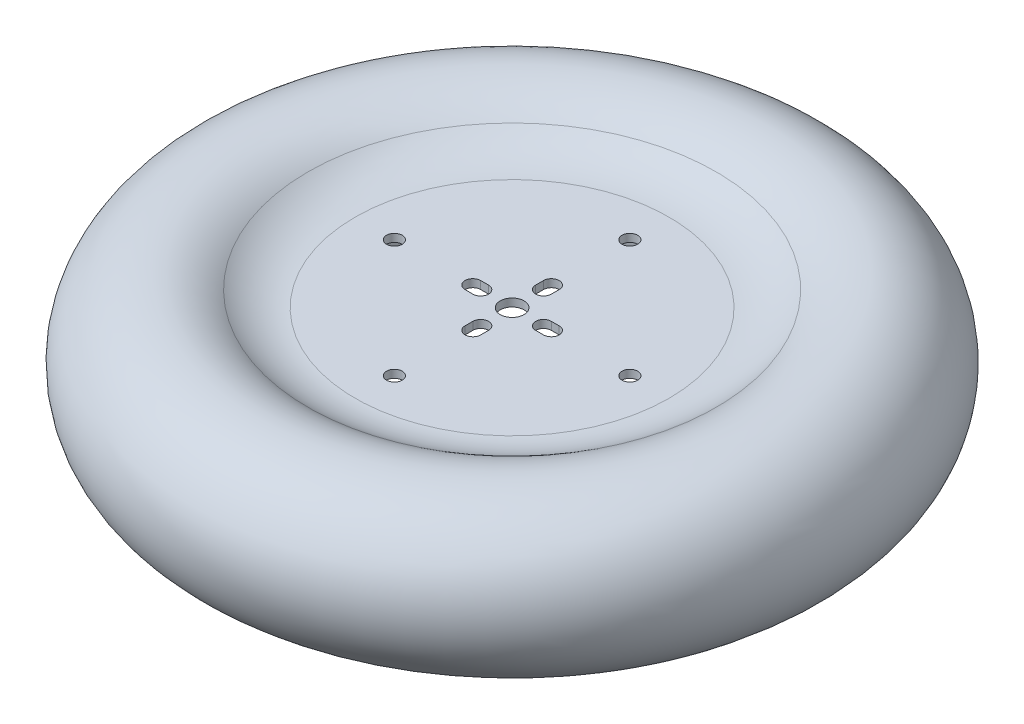
SolidWorks part; units mm, degrees
material "Silicon Rubber"
ref_plane "Front Plane" through (0, 0, 0) normal (0, 0, 1) x (1, 0, 0)
ref_plane "Top Plane" through (0, 0, 0) normal (0, 1, 0) x (1, 0, 0)
ref_plane "Right Plane" through (0, 0, 0) normal (1, 0, 0) x (0, 0, -1)
sketch "Sketch1" plane through (0, 0, 0) normal (0, 0, 1) x (1, 0, 0)
  line L2 (-85, 25) -> (0, 25)
  line L3 (0, 30) -> (0, 25)
  line L4 (0, 30) -> (-100, 30)
  arc A0 (-130, 40) -> (-110, 0) centre (-160, 0) ccw
  arc A1 (-85, 25) -> (-110, 0) centre (-85, 0) ccw
  arc A3 (-130, 40) -> (-100, 30) centre (-100, 80) ccw
  point P6 (-155, 0)
  point P11 (-180, 0)
  dimension "D3" = 100
  dimension "D2" = 50
  dimension "D1" = 160
  dimension "D4" = 30
  dimension "D5" = 5
revolve "Revolve1" add sketch "Sketch1" angle 360 about L3
sketch "Sketch2" plane through (0, 30, 0) normal (0, 1, 0) x (1, 0, 0)
  line L0 (0, 20) -> (0, 25) construction
  line L1 (-5, 20) -> (-5, 25)
  line L2 (5, 20) -> (5, 25)
  line L3 (20, 0) -> (25, 0) construction
  line L4 (20, 5) -> (25, 5)
  line L5 (20, -5) -> (25, -5)
  line L6 (0, -20) -> (0, -25) construction
  line L7 (5, -20) -> (5, -25)
  line L8 (-5, -20) -> (-5, -25)
  line L12 (0, 0) -> (0, 20) construction
  line L13 (20, 0) -> (25, 0) construction
  line L14 (20, 5) -> (25, 5)
  line L15 (20, -5) -> (25, -5)
  line L16 (0, -20) -> (0, -25) construction
  line L17 (5, -20) -> (5, -25)
  line L18 (-5, -20) -> (-5, -25)
  line L19 (-20, 0) -> (-25, 0) construction
  line L20 (-20, -5) -> (-25, -5)
  line L21 (-20, 5) -> (-25, 5)
  line L22 (0, 0) -> (0, 20) construction
  line L44 (-20, 0) -> (-25, 0) construction
  line L45 (-20, -5) -> (-25, -5) [skipped]
  line L46 (-20, 5) -> (-25, 5) [skipped]
  line L47 (-20, 0) -> (-25, 0) construction
  line L48 (-20, -5) -> (-25, -5) [skipped]
  line L49 (-20, 5) -> (-25, 5) [skipped]
  circle A0 centre (0, 75) radius 5
  arc A1 (-5, 20) -> (5, 20) centre (0, 20) ccw
  arc A2 (5, 25) -> (-5, 25) centre (0, 25) ccw
  circle A3 centre (0, 0) radius 7.5967
  circle A4 centre (75, 0) radius 5
  arc A5 (20, 5) -> (20, -5) centre (20, 0) ccw
  arc A6 (25, -5) -> (25, 5) centre (25, 0) ccw
  circle A7 centre (0, -75) radius 5
  arc A8 (5, -20) -> (-5, -20) centre (0, -20) ccw
  arc A9 (-5, -25) -> (5, -25) centre (0, -25) ccw
  circle A10 centre (-75, 0) radius 5
  circle A13 centre (75, 0) radius 5
  arc A14 (20, 5) -> (20, -5) centre (20, 0) ccw
  arc A15 (25, -5) -> (25, 5) centre (25, 0) ccw
  circle A16 centre (0, -75) radius 5
  arc A17 (5, -20) -> (-5, -20) centre (0, -20) ccw
  arc A18 (-5, -25) -> (5, -25) centre (0, -25) ccw
  circle A19 centre (-75, 0) radius 5
  arc A20 (-20, -5) -> (-20, 5) centre (-20, 0) ccw
  arc A21 (-25, 5) -> (-25, -5) centre (-25, 0) ccw
  arc A38 (-20, -5) -> (-20, 5) centre (-20, 0) ccw [skipped]
  arc A39 (-25, 5) -> (-25, -5) centre (-25, 0) ccw [skipped]
  point P2 (0, 22.5)
  point P17 (22.5, 0)
  point P26 (0, -22.5)
  point P42 (-20, 0)
  point P46 (22.5, 0)
  point P55 (0, -22.5)
  point P64 (-22.5, 0)
  point P79 (-20, 0)
  point P86 (-25, 0)
  point P93 (-25, 0)
  point P100 (-22.5, 0)
  point P107 (-22.5, 0)
  point P114 (-22.5, 0)
  point P121 (-22.5, 0)
  point P128 (-22.5, 0)
  dimension "D1" = 10
  dimension "D4" = 5
  dimension "D2" = 75
  dimension "D3" = 5
  dimension "D5" = 20
  dimension "D8" = 20
  dimension "D7" = 4
  dimension "D9" = 4
extrude "Cut-Extrude2" cut sketch "Sketch2" against normal blind 10 contours A10 | A3 | L2 A2 L1 A1 | A4 | L5 A6 L4 A5 | L8 A9 L7 A8 | A7 | A0 | L21 A21 L20 A20 region at (0, 30, -22.5) region at (22.5, 30, 0) region at (0, 30, 22.5) region at (-22.5, 30, 0) region at (0, 30, -75) region at (0, 30, 0) region at (75, 30, 0) region at (0, 30, 75) region at (-75, 30, 0)
